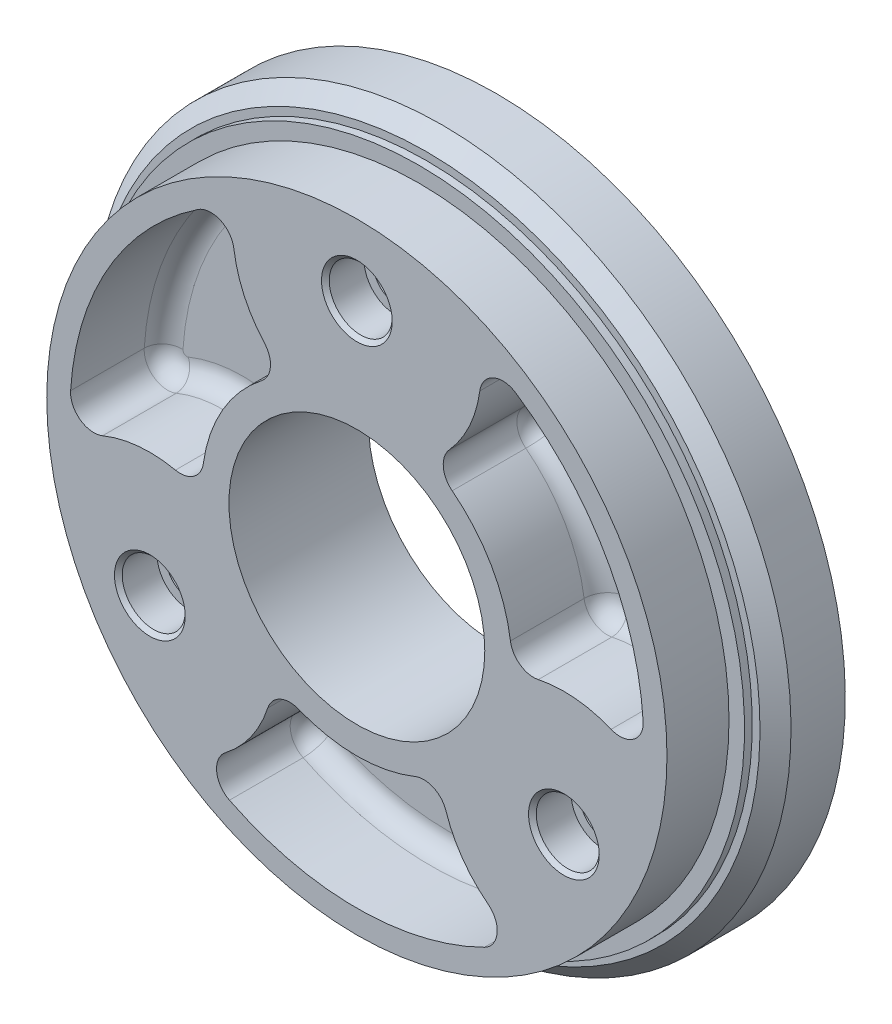
SolidWorks part; units mm, degrees
ref_plane "Front Plane" through (0, 0, 0) normal (0, 0, 1) x (1, 0, 0)
ref_plane "Top Plane" through (0, 0, 0) normal (0, 1, 0) x (1, 0, 0)
ref_plane "Right Plane" through (0, 0, 0) normal (1, 0, 0) x (0, 0, -1)
sketch "Sketch2" plane through (0, 0, 0) normal (1, 0, 0) x (0, 0, -1)
  line L0 (0, 0) -> (0, 50.8)
  line L3 (11.43, 57.15) -> (22.86, 57.15)
  line L4 (22.86, 57.15) -> (22.86, 0)
  line L5 (22.86, 0) -> (0, 0)
  line L7 (0, 50.8) -> (10.16, 50.8)
  line L8 (10.16, 50.8) -> (10.16, 53.34)
  line L9 (10.16, 53.34) -> (11.43, 53.34)
  line L10 (11.43, 53.34) -> (11.43, 57.15)
  dimension "D1" = 12.7
  dimension "D2" = 22.86
  dimension "D4" = 57.15
  dimension "D5" = 50.8
  dimension "D7" = 53.34
  dimension "D8" = 11.43
revolve "Revolve1" add sketch "Sketch2" angle 360 about L5
sketch "Sketch3" plane through (0, 0, 0) normal (0, 0, 1) x (1, 0, 0)
  point P0 (0, 39.1583)
  dimension "D1" = 39.1583
hole_wizard "CBORE for 1/4 Socket Shoulder Screw2" positions "Sketch3" profile "Sketch4" counterbore size "1/4" standard "ANSI Inch" end condition through all
sketch "Sketch4" plane through (0, 39.1583, 0) normal (1, 0, 0) x (0, -1, 0)
  line L0 (0, 0) -> (0, 22.86)
  line L1 (0, 22.86) -> (3.5712, 22.86)
  line L3 (3.5712, 22.86) -> (3.5712, 6.35)
  line L4 (3.5712, 6.35) -> (5.1587, 6.35)
  line L5 (5.1587, 6.35) -> (5.1587, 0)
  line L7 (5.1587, 0) -> (0, 0)
  line L11 (0, -6.35) -> (0, 107.95) construction
  dimension "Thru Hole Dia." = 7.1425
  dimension "Thru Hole Depth" = 22.86
  dimension "C'Bore Dia." = 10.3175
  dimension "C'Bore Depth" = 6.35
sketch "Sketch5" plane through (0, 0, 0) normal (0, 0, 1) x (1, 0, 0)
  line L0 (0, 0) -> (0, 57.15) construction
  line L1 (0, 0) -> (49.4934, 28.575) construction
  circle A1 centre (0, 39.1583) radius 5.1587 construction
  circle A2 centre (0, 39.1583) radius 5.1587 construction
  arc A3 (26.0262, 39.1241) -> (46.8956, 2.9773) centre (0, 0) cw
  arc A4 (15.6141, 20.034) -> (25.157, 3.5052) centre (0, 0) cw
  arc A6 (15.6141, 20.034) -> (15.121, 25.5842) centre (17.9562, 23.0391) cw
  arc A7 (20.1398, 36.4582) -> (15.121, 25.5842) centre (0, 39.1583) cw
  arc A9 (26.0262, 39.1241) -> (20.1398, 36.4582) centre (23.916, 35.9519) ccw
  arc A10 (25.157, 3.5052) -> (29.7171, 0.3031) centre (28.9305, 4.031) ccw
  arc A11 (41.6436, -0.7875) -> (29.7171, 0.3031) centre (33.9121, -19.5792) ccw
  arc A12 (46.8956, 2.9773) -> (41.6436, -0.7875) centre (43.0932, 2.7359) cw
  arc A13 (20.8693, -42.1014) -> (-20.8693, -42.1014) centre (0, 0) cw
  arc A14 (20.8693, -42.1014) -> (21.5038, -35.6707) centre (19.1772, -38.6878) ccw
  arc A15 (21.5038, -35.6707) -> (14.5961, -25.8873) centre (33.9121, -19.5792) cw
  arc A16 (9.5429, -23.5392) -> (14.5961, -25.8873) centre (10.9743, -27.0701) cw
  arc A17 (9.5429, -23.5392) -> (-9.5429, -23.5392) centre (0, 0) cw
  arc A18 (-9.5429, -23.5392) -> (-14.5961, -25.8873) centre (-10.9743, -27.0701) ccw
  arc A19 (-21.5038, -35.6707) -> (-14.5961, -25.8873) centre (-33.9121, -19.5792) ccw
  arc A20 (-20.8693, -42.1014) -> (-21.5038, -35.6707) centre (-19.1772, -38.6878) cw
  arc A21 (-46.8956, 2.9773) -> (-26.0262, 39.1241) centre (0, 0) cw
  arc A22 (-46.8956, 2.9773) -> (-41.6436, -0.7875) centre (-43.0932, 2.7359) ccw
  arc A23 (-41.6436, -0.7875) -> (-29.7171, 0.3031) centre (-33.9121, -19.5792) cw
  arc A24 (-25.157, 3.5052) -> (-29.7171, 0.3031) centre (-28.9305, 4.031) cw
  arc A25 (-25.157, 3.5052) -> (-15.6141, 20.034) centre (0, 0) cw
  arc A26 (-15.6141, 20.034) -> (-15.121, 25.5842) centre (-17.9562, 23.0391) ccw
  arc A27 (-20.1398, 36.4582) -> (-15.121, 25.5842) centre (0, 39.1583) ccw
  arc A28 (-26.0262, 39.1241) -> (-20.1398, 36.4582) centre (-23.916, 35.9519) cw
  circle A29 centre (0, 0) radius 57.15 construction
  point P55 (0, 0)
  dimension "D1" = 25.4
  dimension "D2" = 46.99
  dimension "D3" = 60
  dimension "D4" = 20.32
  dimension "D5" = 3.81
  dimension "D6" = 3
extrude "Cut-Extrude1" cut sketch "Sketch5" against normal blind 15.24
sketch "Sketch7" plane through (0, 0, 0) normal (0, 0, 1) x (1, 0, 0)
  circle A13 centre (0, 0) radius 20.955
  dimension "D1" = 41.91
extrude "Cut-Extrude2" cut sketch "Sketch7" against normal through all
pattern_circular "CirPattern1" count 3 over 360 about axis through (0, 0, -22.86) along (0, 0, -1) of "CBORE for 1/4 Socket Shoulder Screw2" reverse direction yes
chamfer "Chamfer1" distance 0.635 angle 45 3 edges at (-36.4915, -15.1116, 0) (31.3327, -24.0468, 0) (5.1587, 39.1583, 0)
fillet "Fillet1" radius 3.175 24 edges at (12.5798, -23.6149, -15.24) (17.3128, -31.2994, -15.24) (22.9688, -39.0619, -15.24) (0, -46.99, -15.24) (-22.9688, -39.0619, -15.24) (-17.3128, -31.2994, -15.24) (-12.5798, -23.6149, -15.24) (0, -25.4, -15.24) (-26.741, 0.913, -15.24) (-35.7625, 0.6564, -15.24) (-45.313, -0.3606, -15.24) (-40.6945, 23.495, -15.24) (-22.3442, 39.4225, -15.24) (-18.4497, 30.643, -15.24) (-14.1612, 22.7019, -15.24) (-21.997, 12.7, -15.24) (18.4497, 30.643, -15.24) (22.3442, 39.4225, -15.24) (40.6945, 23.495, -15.24) (45.313, -0.3606, -15.24) (35.7625, 0.6564, -15.24) (26.741, 0.913, -15.24) (21.997, 12.7, -15.24) (14.1612, 22.7019, -15.24)
sketch "Sketch8" plane through (0, 0, -22.86) normal (0, 0, -1) x (-1, 0, 0)
  circle A0 centre (0, 39.1583) radius 3.5712 construction
  circle A1 centre (0, 39.1583) radius 3.5712
  circle A2 centre (0, 39.1583) radius 14.2875
  circle A3 centre (33.9121, -19.5792) radius 14.2875
  circle A4 centre (-33.9121, -19.5792) radius 14.2875
  point P10 (0, 0)
  dimension "D1" = 28.575
  dimension "D2" = 3
extrude "Cut-Extrude3" cut sketch "Sketch8" against normal blind 7.9375
sketch "Sketch9" plane through (0, 0, -14.9225) normal (0, 0, -1) x (-1, 0, 0)
  circle A0 centre (0, 39.1583) radius 11.5887
  circle A1 centre (33.9121, -19.5792) radius 11.5887
  circle A2 centre (-33.9121, -19.5792) radius 11.5888
  point P9 (0, 0)
  dimension "D1" = 23.1775
  dimension "D2" = 3
extrude "Cut-Extrude4" cut sketch "Sketch9" against normal blind 1.27
chamfer "Chamfer2" distance 2.54 angle 45 1 edges at (0, 57.15, -11.43)
